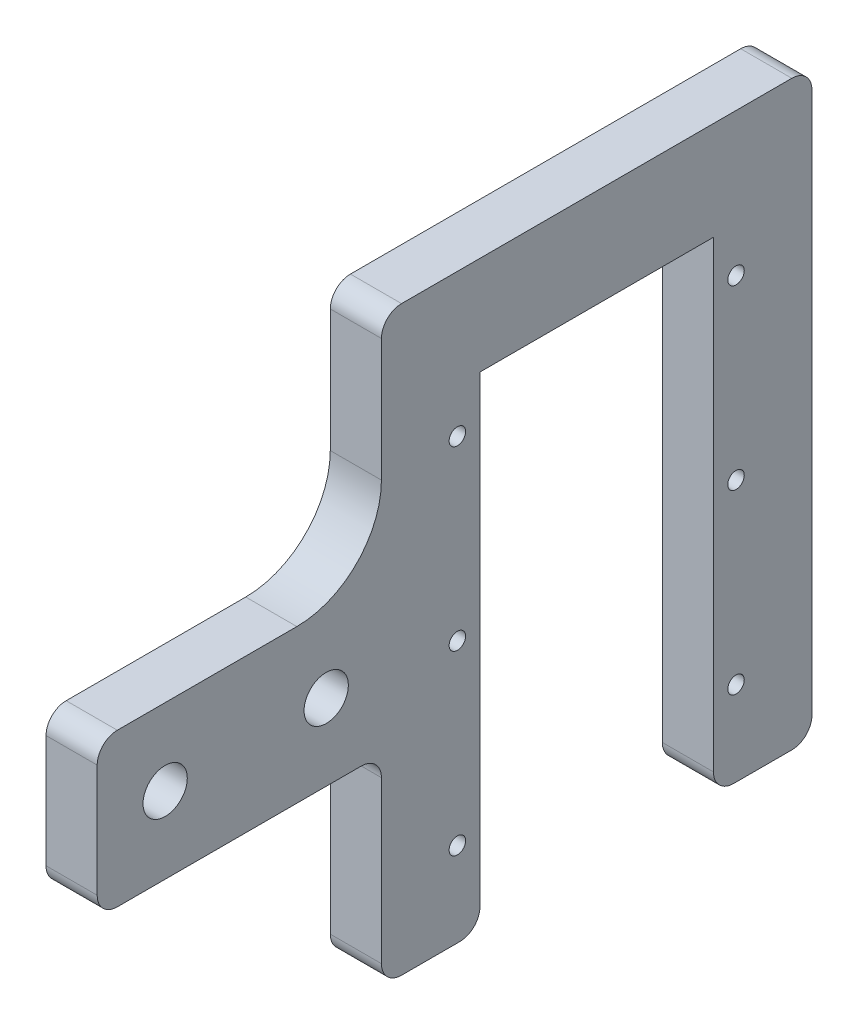
SolidWorks part; units mm, degrees
ref_plane "Front Plane" through (0, 0, 0) normal (0, 0, 1) x (1, 0, 0)
ref_plane "Top Plane" through (0, 0, 0) normal (0, 1, 0) x (1, 0, 0)
ref_plane "Right Plane" through (0, 0, 0) normal (1, 0, 0) x (0, 0, -1)
sketch "Sketch11" plane through (0, 0, 0) normal (1, 0, 0) x (0, 0, -1)
  line L0 (-62.0272, -19) -> (-62.0272, -12) construction
  line L1 (-62.0272, -25) -> (-62.0272, -6)
  line L2 (-62.0272, -25) -> (-25.1472, -25)
  line L3 (-25.1472, -25) -> (-25.1472, -6)
  line L4 (-62.0272, -6) -> (-25.1472, -6)
  line L6 (-515, -6) -> (-15, -6) construction
  line L7 (-25.1472, -12) -> (-25.1472, -19) construction
  point P6 (-62.0272, -15.5)
extrude "Boss-Extrude3" add sketch "Sketch11" along normal mid plane 6.35 separate body
sketch "Sketch8" plane through (0, 0, 0) normal (1, 0, 0) x (0, 0, -1)
  line L0 (0, 10) -> (0, 22.2316) construction
  line L1 (0, 5.5716) -> (0, -5.5716) construction
  line L16 (14.5, 10) -> (14.5, -50)
  line L17 (14.5, -50) -> (26.7316, -50)
  line L18 (26.7316, -50) -> (26.7316, 22.2316)
  line L19 (26.7316, 22.2316) -> (-26.7316, 22.2316)
  line L20 (-26.7316, 22.2316) -> (-26.7316, -50)
  line L21 (-26.7316, -50) -> (-14.5, -50)
  line L22 (-14.5, -50) -> (-14.5, 10)
  line L23 (-14.5, 10) -> (14.5, 10)
  dimension "D2" = 29
  dimension "D4" = 60
extrude "Boss-Extrude2" add sketch "Sketch8" along normal mid plane 6.35
sketch "Sketch4" plane through (-3.175, 0, 0) normal (-1, 0, 0) x (0, 0, 1)
  line L0 (14.5, -50) -> (14.5, 10) construction
  line L3 (0, 0.0539) -> (0, 22.3365) construction
  line L7 (26.7316, -50) -> (14.5, -50) construction
  line L8 (17.3, -39.5) -> (17.3, -17.5) construction
  line L9 (17.3, -17.5) -> (17.3, 4.5) construction
  circle A0 centre (17.3, -39.5) radius 1.025
  circle A1 centre (-17.3, -39.5) radius 1.025
  circle A2 centre (17.3, -17.5) radius 1.025
  circle A3 centre (-17.3, -17.5) radius 1.025
  circle A4 centre (-17.3, 4.5) radius 1.025
  circle A5 centre (17.3, 4.5) radius 1.025
  point P8 (0, 5.9386)
  point P23 (18.6532, -50)
  point P24 (18.379, -50)
  point P25 (21.3119, -50)
  dimension "D5" = 2.05
  dimension "D1" = 2.8
  dimension "D2" = 10.5
  dimension "D6" = 22
extrude "Cut-Extrude4" cut sketch "Sketch4" against normal through all contours A0 | A2 | A5 | A1 | A3 | A4
hole_wizard "M5 Clearance Hole1" positions "Sketch10" profile "Sketch9" hole size "M5" standard "ANSI Metric" end condition up to next
sketch "Sketch10" plane through (3.175, 0, 0) normal (1, 0, 0) x (0, 0, -1)
  circle A0 centre (-53.5872, -15.5) radius 2.1 construction
  circle A1 centre (-33.5872, -15.5) radius 2.1 construction
  point P0 (-53.5872, -15.5)
  point P5 (-33.5872, -15.5)
sketch "Sketch9" plane through (3.175, -15.5, 53.5872) normal (0, 1, 0) x (0, 0, -1)
  line L0 (0, 0) -> (0, 6.35)
  line L1 (0, 6.35) -> (2.75, 6.35)
  line L2 (2.75, 6.35) -> (2.75, 0)
  line L5 (2.75, 0) -> (0, 0)
  line L11 (0, -6.35) -> (0, 107.95) construction
  dimension "Thru Hole Dia." = 5.5
  dimension "Thru Hole Depth" = 6.35
fillet "Fillet1" radius 2.5 9 edges at (0, -50, -26.7316) (0, -50, -14.5) (0, -50, 14.5) (0, -50, 26.7316) (0, -25, 26.7316) (0, -25, 62.0272) (0, -6, 62.0272) (0, 22.2316, -26.7316) (0, 22.2316, 26.7316)
fillet "Fillet2" radius 10.5 1 edges at (0, -6, 26.7316)
